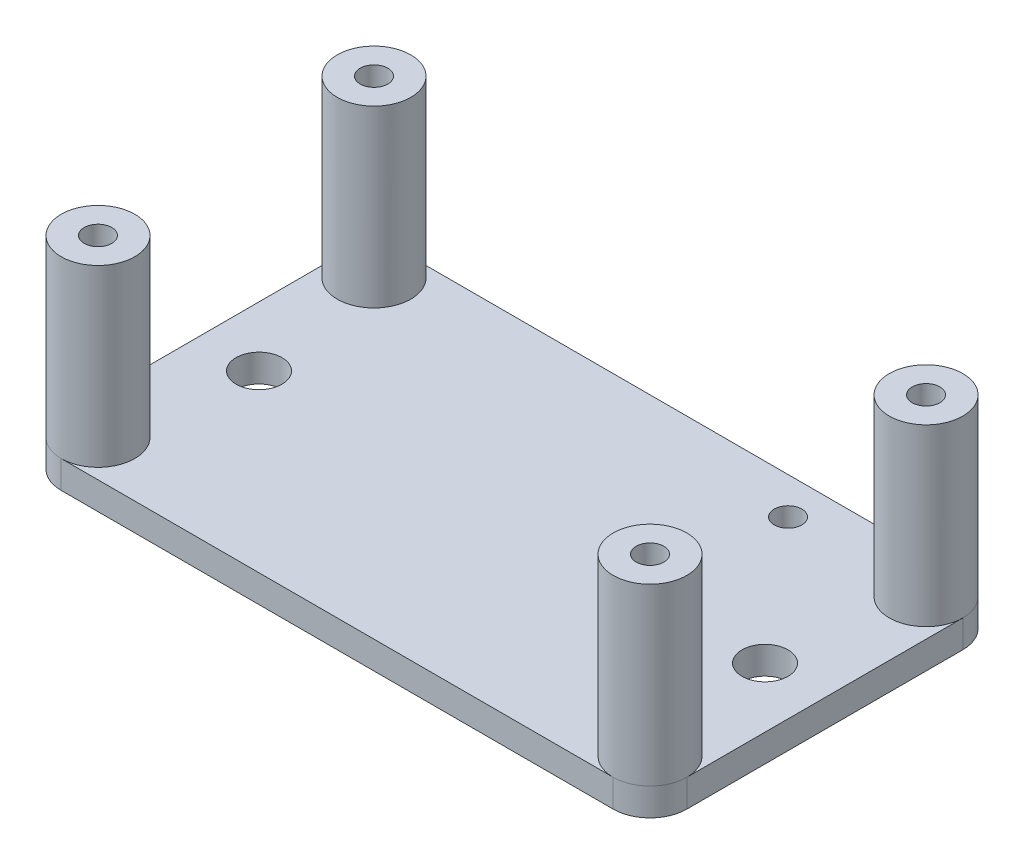
SolidWorks part; units mm, degrees
ref_plane "前视基准面" through (0, 0, 0) normal (0, 0, 1) x (1, 0, 0)
ref_plane "上视基准面" through (0, 0, 0) normal (0, 1, 0) x (1, 0, 0)
ref_plane "右视基准面" through (0, 0, 0) normal (1, 0, 0) x (0, 0, -1)
other "Configuration Table"
sketch "草图1" plane through (0, 0, 0) normal (0, 1, 0) x (1, 0, 0)
  line L0 (-24, 18.1346) -> (-24, -19.8654)
  line L1 (-20, 14.1346) -> (40, 14.1346) construction
  line L2 (-20, 14.1346) -> (-20, -15.8654) construction
  line L3 (-20, -15.8654) -> (40, -15.8654) construction
  line L4 (40, 14.1346) -> (40, -15.8654) construction
  line L5 (-24, -19.8654) -> (44, -19.8654)
  line L6 (44, 18.1346) -> (44, -19.8654)
  line L7 (-24, 18.1346) -> (44, 18.1346)
  line L8 (43.3614, -0.8654) -> (-24.6386, -0.8654) construction
  line L9 (10, 18.1346) -> (10, -19.8654) construction
  circle A0 centre (-20, -15.8654) radius 1.5
  circle A1 centre (-20, 14.1346) radius 1.5
  circle A2 centre (40, 14.1346) radius 1.5
  circle A3 centre (40, -15.8654) radius 1.5
  circle A4 centre (-17.5, -0.8654) radius 2.5
  circle A5 centre (37.5, -0.8654) radius 2.5
  circle A6 centre (25, 14.1346) radius 1.5
  dimension "D3" = 3
  dimension "D5" = 5
  dimension "D7" = 3
  dimension "D8" = 15
  dimension "D1" = 30
  dimension "D2" = 60
  dimension "D6" = 55
  dimension "D4" = 4
extrude "凸台-拉伸1" add sketch "草图1" along normal blind 3
sketch "草图2" plane through (0, 3, 0) normal (0, 1, 0) x (1, 0, 0)
  circle A0 centre (-20, -15.8654) radius 4
  circle A1 centre (-20, -15.8654) radius 1.5
  circle A2 centre (40, -15.8654) radius 1.5
  circle A3 centre (40, -15.8654) radius 4
  circle A4 centre (-20, 14.1346) radius 1.5
  circle A5 centre (-20, 14.1346) radius 4
  circle A6 centre (40, 14.1346) radius 1.5
  circle A7 centre (40, 14.1346) radius 4
  dimension "D1" = 8
extrude "凸台-拉伸2" add sketch "草图2" along normal blind 19
fillet "圆角1" radius 4 4 edges at (44, 1.5, 19.8654) (44, 1.5, -18.1346) (-24, 1.5, -18.1346) (-24, 1.5, 19.8654)
